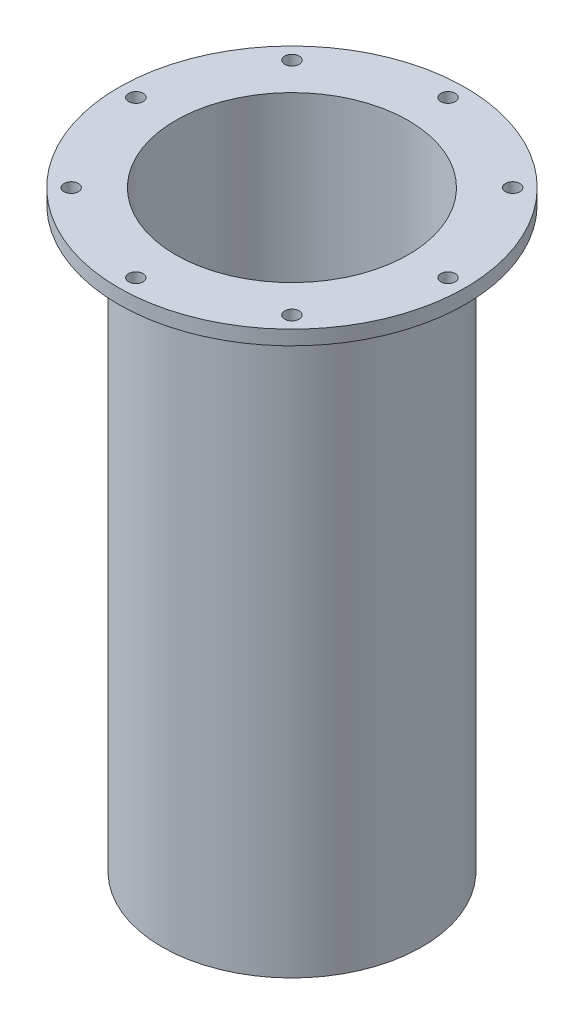
SolidWorks part; units mm, degrees
ref_plane "Front Plane" through (0, 0, 0) normal (0, 0, 1) x (1, 0, 0)
ref_plane "Top Plane" through (0, 0, 0) normal (0, 1, 0) x (1, 0, 0)
ref_plane "Right Plane" through (0, 0, 0) normal (1, 0, 0) x (0, 0, -1)
ref_axis "Axial" through (0, 55, 0) along (0, -1, 0)
sketch "Sketch1" plane through (0, 0, 0) normal (0, 1, 0) x (1, 0, 0)
  circle A0 centre (0, 0) radius 51.1302
  circle A1 centre (0, 0) radius 57.15
  dimension "D1" = 114.3
  dimension "D2" = 102.2604
extrude "Scheduled Chamber" add sketch "Sketch1" against normal blind 260.35
sketch "Sketch2" plane through (0, 0, 0) normal (0, 1, 0) x (1, 0, 0)
  circle A0 centre (0, 0) radius 54.102
  circle A1 centre (0, 0) radius 76.2
  dimension "D1" = 152.4
  dimension "D2" = 108.204
extrude "Flange" add sketch "Sketch2" against normal blind 6.35
sketch "Sketch3" plane through (0, 0, 0) normal (0, 1, 0) x (1, 0, 0)
  line L0 (0, -83.82) -> (0, 83.82) construction
  circle A0 centre (0, 68.58) radius 3.175
  dimension "D1" = 6.35
  dimension "D2" = 68.58
extrude "Original Bolt Hole" cut sketch "Sketch3" against normal up to next
pattern_circular "Bolt Hole Pattern" count 8 over 360 about axis through (0, 55, 0) along (0, -1, 0) of "Original Bolt Hole"
